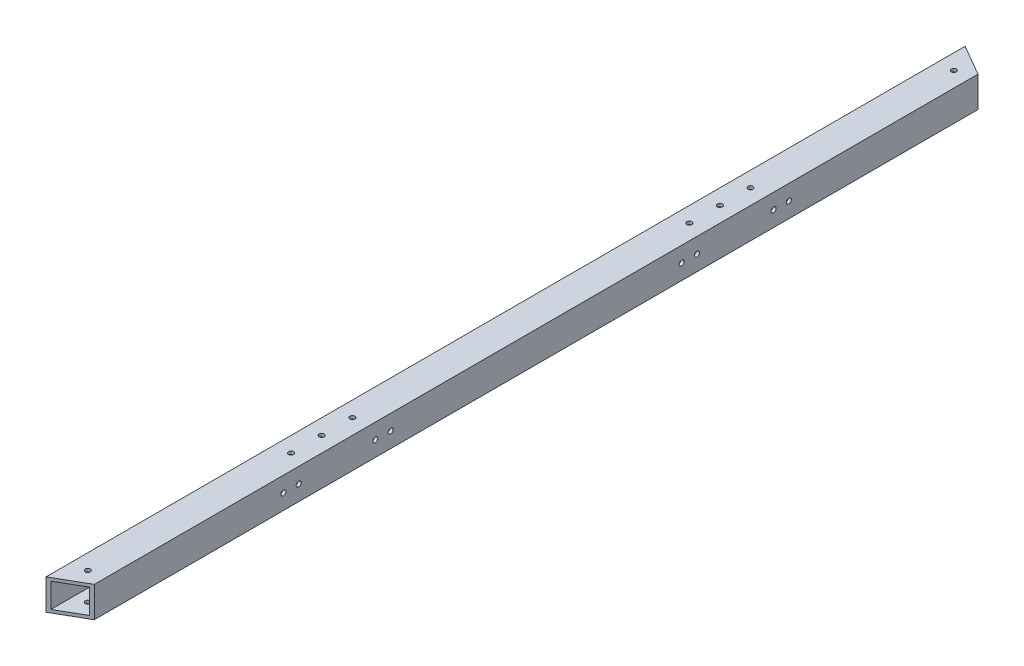
SolidWorks part; units mm, degrees
ref_plane "前视基准面" through (0, 0, 0) normal (0, 0, 1) x (1, 0, 0)
ref_plane "上视基准面" through (0, 0, 0) normal (0, 1, 0) x (1, 0, 0)
ref_plane "右视基准面" through (0, 0, 0) normal (1, 0, 0) x (0, 0, -1)
other "Configuration Table"
sketch "草图1" plane through (0, 0, 0) normal (0, 0, 1) x (1, 0, 0)
  line L1 (-8, -8) -> (8, -8)
  line L2 (-8, -8) -> (-8, 8)
  line L3 (-8, 8) -> (8, 8)
  line L4 (8, -8) -> (8, 8)
  line L5 (-8, -8) -> (8, 8) construction
  line L6 (-8, 8) -> (8, -8) construction
  line L7 (-10, -10) -> (10, -10)
  line L8 (-10, -10) -> (-10, 10)
  line L9 (-10, 10) -> (10, 10)
  line L10 (10, -10) -> (10, 10)
  line L11 (-10, -10) -> (10, 10) construction
  line L12 (-10, 10) -> (10, -10) construction
  point P0 (0, 0)
  point P6 (0, 0)
  dimension "D1" = 20
  dimension "D2" = 2
  dimension "D3" = 2
  dimension "D4" = 20
extrude "凸台-拉伸1" add sketch "草图1" along normal blind 600
sketch "草图2" plane through (0, 10, 0) normal (0, 1, 0) x (1, 0, 0)
  line L0 (-10, 0) -> (10, -11.547)
  line L1 (10, -600) -> (10, 0) construction
  line L2 (10, -11.547) -> (10, 0)
  line L3 (10, 0) -> (-10, 0)
  line L4 (-10, -300) -> (10, -300) construction
  line L5 (-10, -600) -> (-10, 0) construction
  line L6 (10, -600) -> (-10, -600)
  line L7 (10, -588.453) -> (10, -600)
  line L8 (-10, -600) -> (10, -588.453)
  dimension "D1" = 120
extrude "切除-拉伸1" cut sketch "草图2" against normal mid plane 600
sketch "草图3" plane through (0, 10, 0) normal (0, 1, 0) x (1, 0, 0)
  line L0 (-10, -17.3183) -> (10, -17.3183) construction
  line L1 (-10, -600) -> (-10, 0) construction
  line L2 (10, -588.453) -> (10, -11.547) construction
  line L3 (-10, -300) -> (10, -300) construction
  line L4 (10, -11.547) -> (-10, 0) construction
  circle A0 centre (0, -17.3183) radius 1.65
  circle A1 centre (0, -582.6817) radius 1.65
  point P11 (0, -582.6817)
  dimension "D2" = 3.3
  dimension "D1" = 9.9981
extrude "切除-拉伸2" cut sketch "草图3" against normal mid plane 600
sketch "草图4" plane through (0, 0, 0) normal (0, 1, 0) x (1, 0, 0)
  line L0 (0, -17.3183) -> (0, -582.6817) construction
  circle A0 centre (0, -169.9983) radius 1.65
  circle A1 centre (0, -429.9983) radius 1.65
  circle A2 centre (0, -149.9983) radius 1.65
  circle A3 centre (0, -189.9983) radius 1.65
  circle A4 centre (0, -409.9983) radius 1.65
  circle A5 centre (0, -449.9983) radius 1.65
  dimension "D3" = 3.3
  dimension "D4" = 3.3
  dimension "D1" = 260
  dimension "D2" = 152.68
  dimension "D5" = 20
  dimension "D6" = 20
  dimension "D7" = 20
  dimension "D8" = 20
extrude "切除-拉伸3" cut sketch "草图4" against normal mid plane 20
sketch "草图6" plane through (-10, 0, 0) normal (-1, 0, 0) x (0, 0, 1)
  line L0 (0, 0) -> (170, 0) construction
  line L1 (300, -10) -> (300, 10) construction
  line L2 (600, -10) -> (0, -10) construction
  line L3 (600, 10) -> (0, 10) construction
  circle A1 centre (195, 0) radius 1.65
  circle A2 centre (145, 0) radius 1.65
  circle A3 centre (205, 0) radius 1.65
  circle A4 centre (135, 0) radius 1.65
  circle A5 centre (465, 0) radius 1.65
  circle A6 centre (395, 0) radius 1.65
  circle A7 centre (455, 0) radius 1.65
  circle A8 centre (405, 0) radius 1.65
  dimension "D3" = 3.3
  dimension "D4" = 3.3
  dimension "D7" = 3.3
  dimension "D8" = 3.3
  dimension "D1" = 170
  dimension "D5" = 25
  dimension "D6" = 25
  dimension "D9" = 10
  dimension "D10" = 10
extrude "切除-拉伸4" cut sketch "草图6" against normal through all
